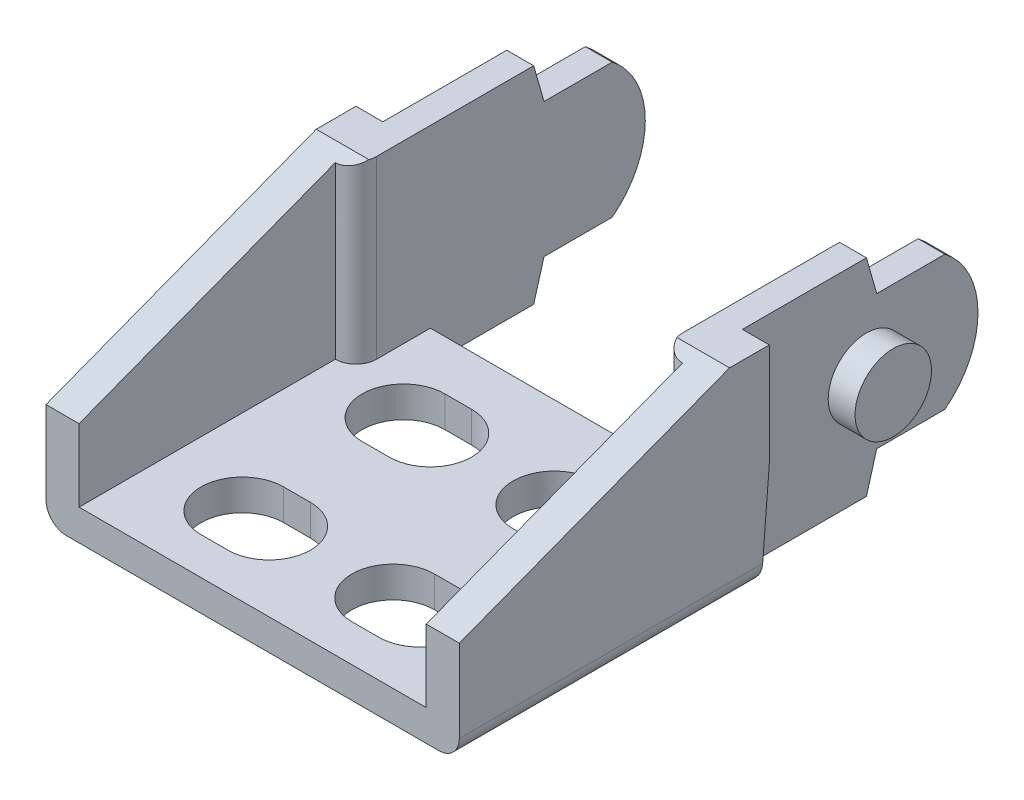
SolidWorks part; units mm, degrees
material "PLA+"
ref_plane "Front Plane" through (0, 0, 0) normal (0, 0, 1) x (1, 0, 0)
ref_plane "Top Plane" through (0, 0, 0) normal (0, 1, 0) x (1, 0, 0)
ref_plane "Right Plane" through (0, 0, 0) normal (1, 0, 0) x (0, 0, -1)
sketch "Sketch1" plane through (0, 0, 0) normal (0, 1, 0) x (1, 0, 0)
  line L1 (10, -8) -> (-10, -8)
  line L2 (10, -8) -> (10, 8)
  line L3 (10, 8) -> (-10, 8)
  line L4 (-10, -8) -> (-10, 8)
  line L5 (10, -8) -> (-10, 8) construction
  line L6 (10, 8) -> (-10, -8) construction
  point P0 (0, 0)
  dimension "D1" = 20
  dimension "D2" = 16
extrude "Boss-Extrude1" add sketch "Sketch1" along normal blind 1.5
sketch "Sketch2" plane through (-10, 0, 0) normal (-1, 0, 0) x (0, 0, 1)
  line L0 (8, 0) -> (8, 5)
  line L1 (8, 5) -> (-5.0767, 10)
  line L2 (-5.0767, 10) -> (-13, 10)
  line L3 (-13, 10) -> (-13.5, 8.25)
  line L4 (-13.5, 8.25) -> (-16.8, 8.25)
  line L6 (-16.8, 1.75) -> (-13.5, 1.75)
  line L7 (-13.5, 1.75) -> (-13, 0)
  line L8 (-13, 0) -> (8, 0)
  line L9 (-21.3708, 5) -> (16.8158, 5) construction
  arc A0 (-16.8, 8.25) -> (-16.8, 1.75) centre (-14.2992, 5) ccw
  point P7 (-18.4, 5)
  dimension "D1" = 5
  dimension "D2" = 10
  dimension "D3" = 21
  dimension "D4" = 6.5
  dimension "D5" = 0.5
  dimension "D6" = 0.5
  dimension "D7" = 14
  dimension "D8" = 26.4
  dimension "D9" = 1.6
extrude "Boss-Extrude2" add sketch "Sketch2" against normal blind 2.6
sketch "Sketch3" plane through (-7.4, 0, 0) normal (1, 0, 0) x (0, 0, -1)
  line L0 (-8, 1.5) -> (4.4, 1.5)
  line L1 (4.4, 1.5) -> (4.4, 9.7413)
  line L2 (-8, 1.5) -> (-8, 5)
  line L3 (-8, 5) -> (4.4, 9.7413)
  line L4 (-8, 5) -> (5.0767, 10) construction
  dimension "D1" = 12.4
extrude "Cut-Extrude1" cut sketch "Sketch3" against normal blind 1
sketch "Sketch4" plane through (-10, 0, 0) normal (-1, 0, 0) x (0, 0, 1)
  line L0 (-13, 0) -> (8, 0) construction
  line L1 (-18.6729, 10) -> (-7, 10)
  line L2 (-18.6729, 10) -> (-18.6729, 0)
  line L3 (-18.6729, 0) -> (-8.7438, 0)
  line L4 (-7, 10) -> (-7, 5)
  line L5 (-5.0767, 10) -> (-13, 10) construction
  line L6 (-7, 5) -> (-6.6, 0)
  line L7 (-6.6, 0) -> (-8.7438, 0)
  line L8 (8, 5) -> (8, 0) construction
  circle A0 centre (-13, 5) radius 1.85
  dimension "D1" = 3.7
  dimension "D2" = 15
  dimension "D3" = 6
  dimension "D4" = 14.6
extrude "Cut-Extrude2" cut sketch "Sketch4" against normal blind 1.3
mirror "Mirror1" about plane through (0, 0, 0) normal (1, 0, 0) of "Cut-Extrude2", "Cut-Extrude1", "Boss-Extrude2"
sketch "Sketch5" plane through (0, 0, 0) normal (0, -1, 0) x (1, 0, 0)
  line L0 (-4.3, 4.2) -> (-3, 4.2) construction
  line L1 (-4.3, 6.2) -> (-3, 6.2)
  line L2 (-4.3, 2.2) -> (-3, 2.2)
  line L3 (3, 4.2) -> (4.3, 4.2) construction
  line L4 (3, 6.2) -> (4.3, 6.2)
  line L5 (3, 2.2) -> (4.3, 2.2)
  line L6 (-4.3, -3.6) -> (-3, -3.6) construction
  line L7 (-4.3, -1.6) -> (-3, -1.6)
  line L8 (-4.3, -5.6) -> (-3, -5.6)
  line L9 (3, -3.6) -> (4.3, -3.6) construction
  line L10 (3, -1.6) -> (4.3, -1.6)
  line L11 (3, -5.6) -> (4.3, -5.6)
  line L12 (-10, 8) -> (10, 8) construction
  line L13 (7.4, -8) -> (-7.4, -8) construction
  line L14 (0, 0) -> (0, 4.2) construction
  arc A0 (-4.3, 6.2) -> (-4.3, 2.2) centre (-4.3, 4.2) ccw
  arc A1 (-3, 2.2) -> (-3, 6.2) centre (-3, 4.2) ccw
  arc A2 (3, 6.2) -> (3, 2.2) centre (3, 4.2) ccw
  arc A3 (4.3, 2.2) -> (4.3, 6.2) centre (4.3, 4.2) ccw
  arc A4 (-4.3, -1.6) -> (-4.3, -5.6) centre (-4.3, -3.6) ccw
  arc A5 (-3, -5.6) -> (-3, -1.6) centre (-3, -3.6) ccw
  arc A6 (3, -1.6) -> (3, -5.6) centre (3, -3.6) ccw
  arc A7 (4.3, -5.6) -> (4.3, -1.6) centre (4.3, -3.6) ccw
  point P2 (-3.65, 4.2)
  point P7 (3.65, 4.2)
  point P14 (-3.65, -3.6)
  point P21 (3.65, -3.6)
  point P33 (1, 4.2)
  point P34 (6.3, 4.2)
  point P39 (-1, -3.6)
  point P40 (1, -3.6)
  dimension "D1" = 4
  dimension "D2" = 5.3
  dimension "D3" = 1.8
  dimension "D4" = 2.4
  dimension "D5" = 2
extrude "Cut-Extrude3" cut sketch "Sketch5" against normal blind 4.3
fillet "Fillet1" radius 1 4 edges at (-7.4, 5.6206, -4.4) (10, 0, 0.7) (-10, 0, 0.7) (7.4, 5.6206, -4.4)
